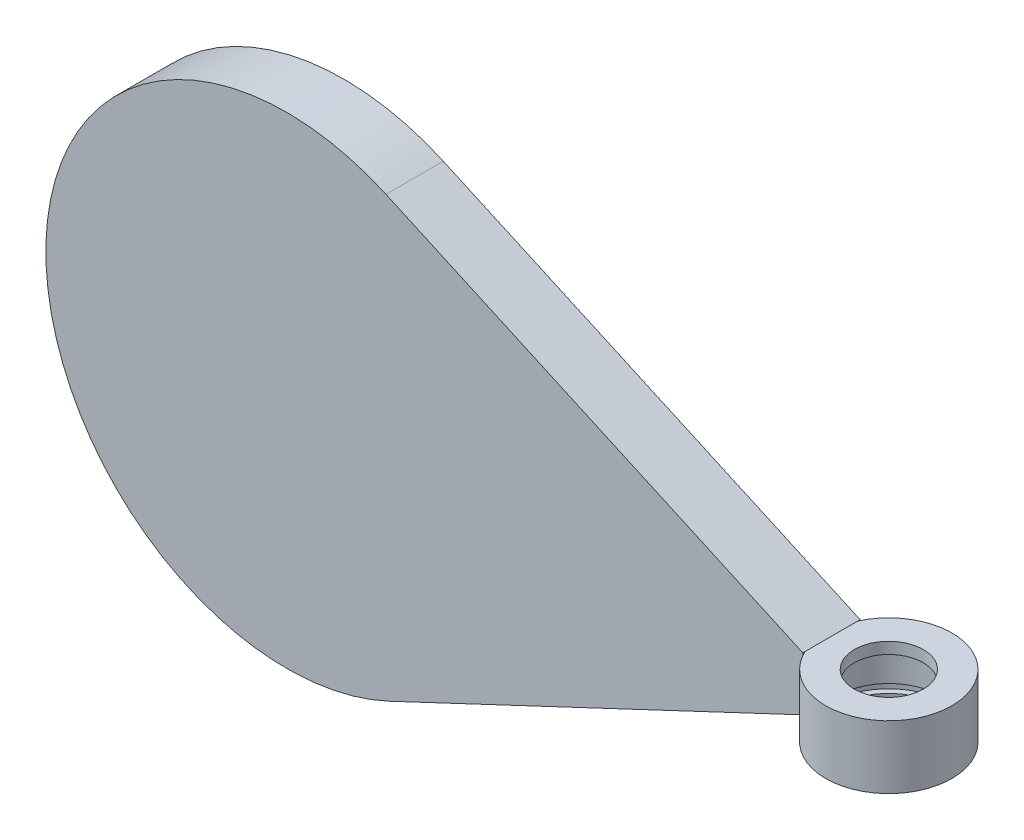
SolidWorks part; units mm, degrees
ref_plane "前视基准面" through (0, 0, 0) normal (0, 0, 1) x (1, 0, 0)
ref_plane "上视基准面" through (0, 0, 0) normal (0, 1, 0) x (1, 0, 0)
ref_plane "右视基准面" through (0, 0, 0) normal (1, 0, 0) x (0, 0, -1)
other "Configuration Table"
sketch "草图1" plane through (0, 0, 0) normal (0, 0, 1) x (1, 0, 0)
  circle A0 centre (0, 0) radius 42
  dimension "D1" = 84
extrude "凸台-拉伸1" add sketch "草图1" along normal blind 5
sketch "草图2" plane through (0, 0, 5) normal (0, 0, 1) x (1, 0, 0)
  line L0 (0, 0) -> (150.9371, 0) construction
  line L1 (100, 22.7173) -> (100, -21.6499) construction
  line L3 (89, 5.375) -> (100, 5.375)
  line L4 (89, 5.375) -> (89, -5.625)
  line L8 (89, -5.625) -> (100, -5.625)
  line L9 (100, 5.375) -> (100, -5.625)
  dimension "D2" = 11
  dimension "D1" = 100
  dimension "D3" = 5.375
  dimension "D4" = 11
revolve "旋转1" add sketch "草图2" angle 360 about L1
sketch "草图3" plane through (0, 0, 5) normal (0, 0, 1) x (1, 0, 0)
  line L0 (17.3147, 38.2649) -> (90, 5.375)
  line L1 (17.9116, -37.9891) -> (90, -4)
  line L4 (90, 5.375) -> (90, -4)
  circle A1 centre (0, 0) radius 42
  arc A2 (17.3147, 38.2649) -> (17.9116, -37.9891) centre (0, 0) ccw
  dimension "D2" = 90
  dimension "D3" = 5.375
  dimension "D4" = 4
  dimension "D1" = 0
extrude "凸台-拉伸2" add sketch "草图3" along normal mid plane 10
sketch "草图4" plane through (0, -5.625, 0) normal (0, -1, 0) x (1, 0, 0)
  circle A0 centre (100, 5) radius 6
  dimension "D1" = 12
extrude "切除-拉伸1" cut sketch "草图4" against normal blind 25
sketch "草图5" plane through (0, -5.625, 0) normal (0, -1, 0) x (1, 0, 0)
  circle A0 centre (100, 5) radius 9
  dimension "D1" = 18
extrude "切除-拉伸2" cut sketch "草图5" against normal offset from surface (9 mm away) 2 up to face at (100, 5.375, 11)
sketch "草图6" plane through (0, 3.375, 0) normal (0, -1, 0) x (1, 0, 0)
  circle A0 centre (100, 5) radius 10
  circle A1 centre (100, 5) radius 9 construction
  circle A2 centre (100, 5) radius 9 construction
  circle A3 centre (100, 5) radius 9
  circle M1 centre (100, 5) radius 9
  dimension "D1" = 1
extrude "切除-拉伸3" cut sketch "草图6" along normal blind 1.5 from offset 6.5 contours A0 M1 region at (90.2828, 3.375, 5)
